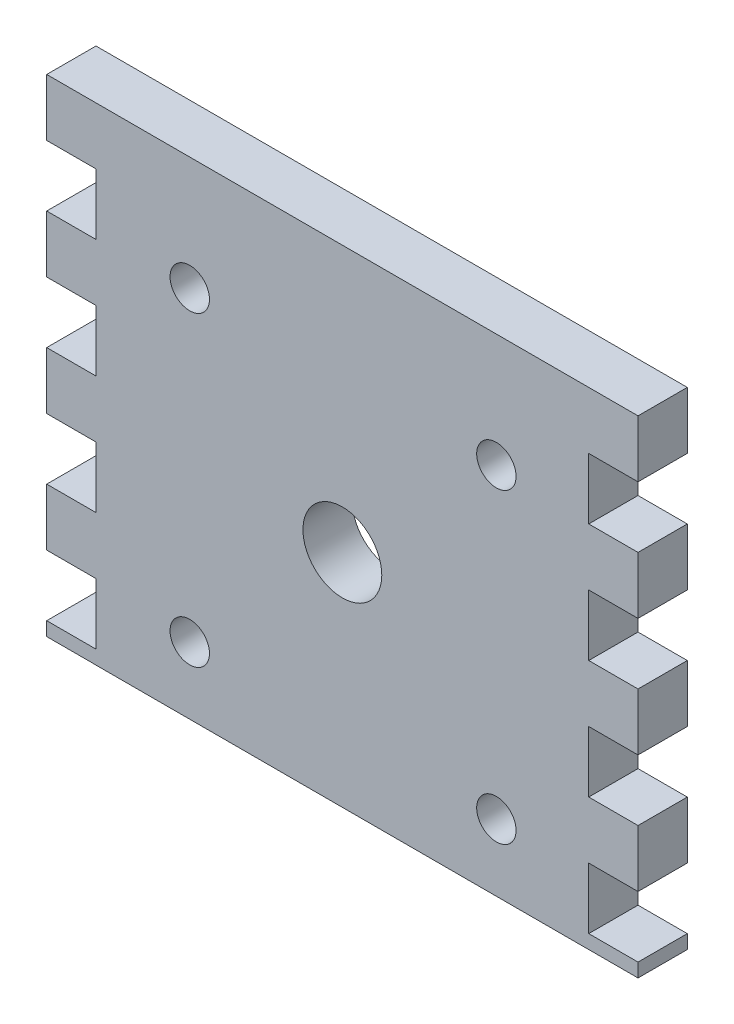
SolidWorks part; units mm, degrees
ref_plane "Front Plane" through (0, 0, 0) normal (0, 0, 1) x (1, 0, 0)
ref_plane "Top Plane" through (0, 0, 0) normal (0, 1, 0) x (1, 0, 0)
ref_plane "Right Plane" through (0, 0, 0) normal (1, 0, 0) x (0, 0, -1)
sketch "Sketch1" plane through (0, 0, 0) normal (0, 0, 1) x (1, 0, 0)
  line L1 (-37.8801, 17.0433) -> (38.3199, 17.0433)
  line L2 (-37.8801, 17.0433) -> (-37.8801, -59.1567)
  line L3 (-37.8801, -59.1567) -> (38.3199, -59.1567)
  line L4 (38.3199, 17.0433) -> (38.3199, -59.1567)
  dimension "D1" = 76.2
  dimension "D2" = 76.2
extrude "Boss-Extrude1" add sketch "Sketch1" along normal blind 6.35
sketch "Sketch2" plane through (0, 0, 6.35) normal (0, 0, 1) x (1, 0, 0)
  line L0 (-37.8801, 17.0433) -> (-31.5301, 17.0433)
  line L1 (38.3199, 17.0433) -> (-37.8801, 17.0433) construction
  line L2 (-31.5301, 17.0433) -> (-31.5301, 9.4233)
  line L3 (-31.5301, 9.4233) -> (-37.8801, 9.4233)
  line L4 (-37.8801, 17.0433) -> (-37.8801, -59.1567) construction
  line L5 (-37.8801, 9.4233) -> (-37.8801, 1.8033)
  line L6 (-37.8801, 1.8033) -> (-31.5301, 1.8033)
  line L7 (-31.5301, 1.8033) -> (-31.5301, -5.8167)
  line L8 (-31.5301, -5.8167) -> (-37.8801, -5.8167)
  line L9 (-37.8801, -5.8167) -> (-37.8801, -13.4367)
  line L10 (-37.8801, -13.4367) -> (-31.5301, -13.4367)
  line L11 (-31.5301, -13.4367) -> (-31.5301, -21.0567)
  line L12 (-31.5301, -21.0567) -> (-37.8801, -21.0567)
  line L13 (-37.8801, -21.0567) -> (-46.7258, -21.0567)
  line L14 (-37.8801, -21.0567) -> (-37.8801, -28.6767) [skipped]
  line L15 (-46.7258, -21.0567) -> (-46.7258, 17.0433)
  line L16 (-46.7258, 17.0433) -> (-37.8801, 17.0433)
  line L19 (47.1657, -21.0567) -> (47.1657, 17.0433)
  line L20 (38.3199, -21.0567) -> (47.1657, -21.0567)
  line L21 (31.9699, -21.0567) -> (38.3199, -21.0567)
  line L22 (31.9699, -13.4367) -> (31.9699, -21.0567)
  line L23 (38.3199, -13.4367) -> (31.9699, -13.4367)
  line L24 (38.3199, -5.8167) -> (38.3199, -13.4367)
  line L25 (31.9699, -5.8167) -> (38.3199, -5.8167)
  line L26 (31.9699, 1.8033) -> (31.9699, -5.8167)
  line L27 (38.3199, 1.8033) -> (31.9699, 1.8033)
  line L28 (38.3199, 9.4233) -> (38.3199, 1.8033)
  line L29 (31.9699, 9.4233) -> (38.3199, 9.4233)
  line L30 (31.9699, 17.0433) -> (31.9699, 9.4233)
  line L31 (38.3199, 17.0433) -> (31.9699, 17.0433)
  line L32 (47.1657, 17.0433) -> (38.3199, 17.0433)
  dimension "D1" = 7.62
  dimension "D2" = 7.62
  dimension "D3" = 6.35
  dimension "D4" = 6.35
  dimension "D6" = 38.1
  dimension "D5" = 3
extrude "Cut-Extrude1" cut sketch "Sketch2" against normal blind 6.35
sketch "Sketch3" plane through (0, 0, 6.35) normal (0, 0, 1) x (1, 0, 0)
  line L1 (-31.5301, -21.0567) -> (-37.8801, -21.0567)
  line L2 (-31.5301, -21.0567) -> (-31.5301, -59.1567)
  line L3 (-31.5301, -59.1567) -> (-37.8801, -59.1567)
  line L4 (-37.8801, -21.0567) -> (-37.8801, -59.1567)
  line L5 (31.9699, -21.0567) -> (38.3199, -21.0567)
  line L6 (31.9699, -21.0567) -> (31.9699, -59.1567)
  line L7 (31.9699, -59.1567) -> (38.3199, -59.1567)
  line L8 (38.3199, -21.0567) -> (38.3199, -59.1567)
extrude "Cut-Extrude2" cut sketch "Sketch3" against normal blind 6.35
sketch "Sketch4" plane through (0, 0, 6.35) normal (0, 0, 1) x (1, 0, 0)
  line L0 (-31.5301, -13.4367) -> (-31.5301, -21.0567)
  line L1 (-31.5301, -59.1567) -> (-31.5301, -13.4367) construction
  line L2 (-31.5301, -21.0567) -> (-37.8801, -21.0567)
  line L3 (-37.8801, -21.0567) -> (-37.8801, -28.6767)
  line L4 (-37.8801, -28.6767) -> (-31.5301, -28.6767)
  line L5 (-31.5301, -21.0567) -> (-31.5301, -28.6767)
  line L6 (0.2199, 17.0433) -> (0.2199, -59.1567)
  line L7 (31.9699, 17.0433) -> (-31.5301, 17.0433) construction
  line L8 (-31.5301, -59.1567) -> (31.9699, -59.1567) construction
  line L9 (31.9699, -21.0567) -> (38.3199, -21.0567)
  line L10 (38.3199, -21.0567) -> (38.3199, -28.6767)
  line L11 (38.3199, -28.6767) -> (31.9699, -28.6767)
  line L12 (31.9699, -21.0567) -> (31.9699, -28.6767)
  line M6 (-31.5301, -13.4367) -> (-31.5301, -59.1567)
  line M8 (31.9699, -59.1567) -> (31.9699, -13.4367)
  dimension "D1" = 7.62
  dimension "D2" = 7.62
  dimension "D3" = 6.35
  dimension "D4" = 6.35
extrude "Boss-Extrude3" add sketch "Sketch4" against normal blind 6.35 contours L3 L4 L2 M6 | L11 L10 L9 M8 region at (-34.7051, -24.8667, 6.35) region at (35.1449, -24.8667, 6.35)
sketch "Sketch5" plane through (0, 17.0433, 0) normal (0, 1, 0) x (1, 0, 0)
  line L1 (-31.5301, 0) -> (31.9699, 0)
  line L2 (-31.5301, 0) -> (-31.5301, -6.35)
  line L3 (-31.5301, -6.35) -> (31.9699, -6.35)
  line L4 (31.9699, 0) -> (31.9699, -6.35)
extrude "Cut-Extrude3" cut sketch "Sketch5" against normal blind 7.62
sketch "Sketch6" plane through (0, 0, 6.35) normal (0, 0, 1) x (1, 0, 0)
  line L0 (-31.5301, -59.1567) -> (31.9699, -59.1567) construction
  line L1 (-19.4468, -5.1999) -> (0.2199, -24.8667) construction
  line L2 (0.2199, -24.8667) -> (-37.8801, -24.8667) construction
  circle A0 centre (0.2199, -24.8667) radius 5.08
  circle A5 centre (-19.4468, -5.1999) radius 2.54
  circle A6 centre (20.0663, -5.1999) radius 2.54
  circle A7 centre (20.0663, -44.7131) radius 2.54
  circle A8 centre (-19.4468, -44.7131) radius 2.54
  point P16 (0.2825, -24.9292)
  point P18 (0.3097, -24.9565)
  dimension "D3" = 10.16
  dimension "D6" = 4
  dimension "D8" = 5.08
  dimension "D1" = 34.29
  dimension "D2" = 31.75
  dimension "D4" = 45
  dimension "D5" = 27.813
extrude "Cut-Extrude4" cut sketch "Sketch6" against normal through all
sketch "Sketch7" plane through (0, 0, 6.35) normal (0, 0, 1) x (1, 0, 0)
  line L0 (-31.5301, -28.6767) -> (-31.5301, -36.2967)
  line L1 (-31.5301, -59.1567) -> (-31.5301, -28.6767) construction
  line L2 (-31.5301, -36.2967) -> (-37.8801, -36.2967)
  line L3 (31.9699, -28.6767) -> (31.9699, -36.2967)
  line L4 (31.9699, -28.6767) -> (31.9699, -59.1567) construction
  line L5 (31.9699, -36.2967) -> (38.3199, -36.2967)
  line L6 (-37.8801, -36.2967) -> (-37.8801, -43.9167)
  line L7 (-37.8801, -43.9167) -> (-31.5301, -43.9167)
  line L8 (38.3199, -36.2967) -> (38.3199, -43.9167)
  line L9 (38.3199, -43.9167) -> (31.9699, -43.9167)
  line L12 (-31.5301, -43.9167) -> (-31.5301, -59.1567)
  line M27 (-31.5301, -28.6767) -> (-31.5301, -59.1567)
  line M29 (31.9699, -59.1567) -> (31.9699, -28.6767)
  dimension "D1" = 7.62
  dimension "D2" = 6.35
  dimension "D3" = 7.62
  dimension "D4" = 6.35
  dimension "D5" = 7.62
  dimension "D6" = 7.62
  dimension "D7" = 6.35
  dimension "D8" = 6.35
extrude "Boss-Extrude4" add sketch "Sketch7" against normal blind 6.35 contours L6 L7 L2 M27 | L9 L8 L5 M29 region at (-34.7051, -40.1067, 6.35) region at (35.1449, -40.1067, 6.35)
sketch "Sketch8" plane through (0, 0, 6.35) normal (0, 0, 1) x (1, 0, 0)
sketch "Sketch9" plane through (0, 0, 6.35) normal (0, 0, 1) x (1, 0, 0)
  line L0 (-31.5301, -43.9167) -> (-31.5301, -59.1567)
  line L1 (-31.5301, -59.1567) -> (31.9699, -59.1567)
  line L2 (31.9699, -59.1567) -> (31.9699, -43.9167)
  line L3 (31.9699, -43.9167) -> (31.9699, -59.1567) construction
  line L6 (-31.5301, -53.3208) -> (31.9699, -53.3208)
  line L7 (-31.5301, -53.3208) -> (-31.5301, -59.1567)
  line L8 (-31.5301, -59.1567) -> (31.9699, -59.1567)
  line L9 (31.9699, -53.3208) -> (31.9699, -59.1567)
  line M28 (-31.5301, -59.1567) -> (31.9699, -59.1567)
  line M29 (31.9699, -59.1567) -> (31.9699, -43.9167)
extrude "Cut-Extrude5" cut sketch "Sketch9" against normal blind 6.35 contours L6 L0 M28 M29 region at (0.2199, -56.2388, 6.35)
sketch "Sketch10" plane through (0, 1.8033, 0) normal (0, -1, 0) x (1, 0, 0)
  line L0 (38.3199, 0) -> (38.3199, 6.35) construction
  line L1 (31.9699, 0) -> (38.3199, 0)
  line L2 (31.9699, 0) -> (31.9699, 6.35)
  line L3 (31.9699, 6.35) -> (38.3199, 6.35)
  line L4 (38.3199, 0) -> (38.3199, 6.35)
  line L5 (38.3199, 6.35) -> (31.9699, 6.35) construction
  point P9 (31.9699, 0)
  point P10 (31.9699, 0)
extrude "Boss-Extrude5" add sketch "Sketch10" along normal blind 55.118
sketch "Sketch11" plane through (0, 1.8033, 0) normal (0, -1, 0) x (1, 0, 0)
  line L1 (-31.5301, 0) -> (-37.8801, 0)
  line L2 (-31.5301, 0) -> (-31.5301, 6.35)
  line L3 (-31.5301, 6.35) -> (-37.8801, 6.35)
  line L4 (-37.8801, 0) -> (-37.8801, 6.35)
extrude "Boss-Extrude6" add sketch "Sketch11" along normal blind 55.118
sketch "Sketch12" plane through (0, 0, 6.35) normal (0, 0, 1) x (1, 0, 0)
  line L0 (-37.8801, 9.4233) -> (-37.8801, 2.0573)
  line L1 (-37.8801, 9.4233) -> (-37.8801, -53.3147) construction
  line L2 (-37.8801, 2.0573) -> (-31.5301, 2.0573)
  line L3 (-31.5301, 2.0573) -> (-31.5301, -5.8167)
  line L4 (-31.5301, -5.8167) -> (-37.8801, -5.8167)
  line L5 (-37.8801, -5.8167) -> (-37.8801, -13.1827)
  line L6 (-37.8801, -13.1827) -> (-31.5301, -13.1827)
  line L7 (-31.5301, -13.1827) -> (-31.5301, -21.0567)
  line L8 (-31.5301, -21.0567) -> (-37.8801, -21.0567)
  line L9 (-37.8801, -21.0567) -> (-37.8801, -28.4227)
  line L10 (-37.8801, -28.4227) -> (-31.5301, -28.4227)
  line L11 (-31.5301, -28.4227) -> (-31.5301, -36.2967)
  line L12 (-31.5301, -36.2967) -> (-37.8801, -36.2967)
  line L13 (-37.8801, -36.2967) -> (-37.8801, -43.6627)
  line L14 (-37.8801, -43.6627) -> (-31.5301, -43.6627)
  line L15 (-31.5301, -43.6627) -> (-31.5301, -51.5367)
  line L16 (-31.5301, -51.5367) -> (-37.8801, -51.5367)
  line L17 (-37.8801, 9.4233) -> (-56.0123, 9.4233)
  line L18 (-56.0123, 9.4233) -> (-56.0123, -53.8176)
  line L19 (-56.0123, -53.8176) -> (-37.8801, -51.5367)
  line L20 (0.2199, 9.4233) -> (0.2199, -53.3208)
  line L21 (-37.8801, 9.4233) -> (38.3199, 9.4233) construction
  line L22 (-31.5301, -53.3208) -> (31.9699, -53.3208) construction
  line L23 (56.4521, 9.4233) -> (56.4521, -53.8176)
  line L24 (38.3199, 9.4233) -> (56.4521, 9.4233)
  line L25 (38.3199, 9.4233) -> (38.3199, 2.0573)
  line L26 (38.3199, 2.0573) -> (31.9699, 2.0573)
  line L27 (31.9699, 2.0573) -> (31.9699, -5.8167)
  line L28 (31.9699, -5.8167) -> (38.3199, -5.8167)
  line L29 (38.3199, -5.8167) -> (38.3199, -13.1827)
  line L30 (38.3199, -13.1827) -> (31.9699, -13.1827)
  line L31 (31.9699, -13.1827) -> (31.9699, -21.0567)
  line L32 (31.9699, -21.0567) -> (38.3199, -21.0567)
  line L33 (38.3199, -21.0567) -> (38.3199, -28.4227)
  line L34 (38.3199, -28.4227) -> (31.9699, -28.4227)
  line L35 (31.9699, -28.4227) -> (31.9699, -36.2967)
  line L36 (31.9699, -36.2967) -> (38.3199, -36.2967)
  line L37 (38.3199, -36.2967) -> (38.3199, -43.6627)
  line L38 (38.3199, -43.6627) -> (31.9699, -43.6627)
  line L39 (31.9699, -43.6627) -> (31.9699, -51.5367)
  line L40 (31.9699, -51.5367) -> (38.3199, -51.5367)
  line L41 (56.4521, -53.8176) -> (38.3199, -51.5367)
  line M26 (38.3199, -53.3147) -> (38.3199, 9.4233)
  line M28 (-37.8801, 9.4233) -> (-37.8801, -53.3147)
  dimension "D1" = 7.366
  dimension "D2" = 7.874
  dimension "D3" = 6.35
  dimension "D4" = 4
extrude "Cut-Extrude7" cut sketch "Sketch12" against normal blind 55.118 contours L18 L19 L17 M28 | L41 L23 L24 M26 | L39 L40 L38 M26 | L35 L36 L34 M26 | L31 L32 L30 M26 | L27 L28 L26 M26 | L4 L3 L2 M28 | L8 L7 L6 M28 | L12 L11 L10 M28 | L16 L15 L14 M28 region at (-47.0017, -21.6304, 6.35) region at (-34.7051, -1.8797, 6.35) region at (-34.7051, -17.1197, 6.35) region at (-34.7051, -47.5997, 6.35) region at (-34.7051, -32.3597, 6.35) region at (47.4415, -21.6304, 6.35) region at (35.1449, -47.5997, 6.35) region at (35.1449, -1.8797, 6.35) region at (35.1449, -32.3597, 6.35) region at (35.1449, -17.1197, 6.35)
